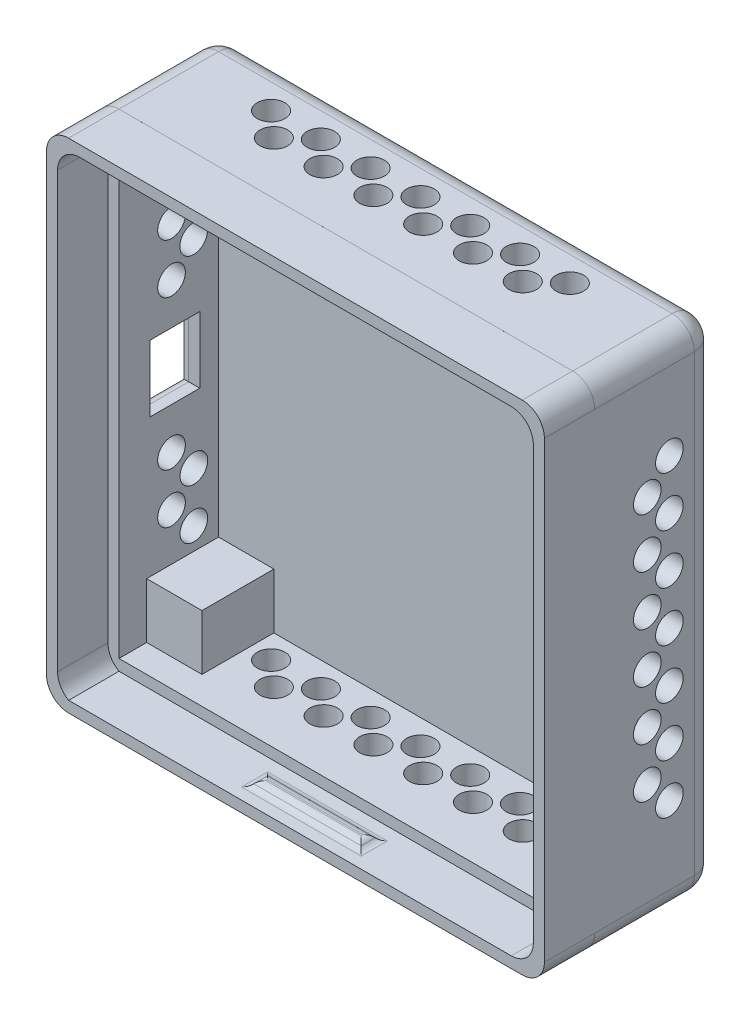
SolidWorks part; units mm, degrees
ref_plane "Piano frontale" through (0, 0, 0) normal (0, 0, 1) x (1, 0, 0)
ref_plane "Piano superiore" through (0, 0, 0) normal (0, 1, 0) x (1, 0, 0)
ref_plane "Piano destro" through (0, 0, 0) normal (1, 0, 0) x (0, 0, -1)
sketch "Schizzo2" plane through (0, 0, 0) normal (0, 0, 1) x (1, 0, 0)
  line L1 (0, 0) -> (45, 0)
  line L2 (0, 0) -> (0, 45)
  line L3 (0, 45) -> (45, 45)
  line L4 (45, 0) -> (45, 45)
  dimension "D1" = 45
  dimension "D2" = 45
extrude "Estrusione-Estrusione2" add sketch "Schizzo2" along normal blind 11
shell "Svuota1" thickness 2 removed face at (22.5, 22.5, 11)
fillet "Raccordo1" radius 2 4 edges at (45, 45, 5.5) (45, 0, 5.5) (0, 0, 5.5) (0, 45, 5.5)
fillet "Raccordo2" radius 2 8 edges at (44.4142, 0.5858, 0) (22.5, 0, 0) (0.5858, 0.5858, 0) (0, 22.5, 0) (0.5858, 44.4142, 0) (22.5, 45, 0) (44.4142, 44.4142, 0) (45, 22.5, 0)
sketch "Schizzo3" plane through (0, 0, 2) normal (0, 0, 1) x (1, 0, 0)
  line L0 (43, 43) -> (2, 43) construction
  line L1 (2, 43) -> (7, 43)
  line L2 (2, 43) -> (2, 38)
  line L3 (2, 38) -> (7, 38)
  line L4 (7, 43) -> (7, 38)
  line L5 (43, 43) -> (2, 43) construction
  dimension "D1" = 5
  dimension "D2" = 5
extrude "Estrusione-Estrusione3" add sketch "Schizzo3" along normal blind 6.5
sketch "Schizzo4" plane through (0, 0, 2) normal (0, 0, 1) x (1, 0, 0)
  line L1 (43, 2) -> (38, 2)
  line L2 (43, 2) -> (43, 7)
  line L3 (43, 7) -> (38, 7)
  line L4 (38, 2) -> (38, 7)
  dimension "D1" = 5
  dimension "D2" = 5
extrude "Estrusione-Estrusione4" add sketch "Schizzo4" along normal blind 6.5
fillet "Raccordo3" radius 4 2 edges at (38, 7, 5.25) (7, 38, 5.25)
sketch "Schizzo5" plane through (0, 0, 2) normal (0, 0, 1) x (1, 0, 0)
  line L0 (43, 2) -> (43, 43) construction
  line L1 (43, 43) -> (38, 43)
  line L2 (43, 43) -> (43, 38)
  line L3 (43, 38) -> (38, 38)
  line L4 (38, 43) -> (38, 38)
  line L5 (43, 43) -> (7, 43) construction
  line L7 (2, 2) -> (7, 2)
  line L8 (2, 2) -> (2, 7)
  line L9 (2, 7) -> (7, 7)
  line L10 (7, 2) -> (7, 7)
  dimension "D1" = 5
  dimension "D2" = 5
  dimension "D3" = 5
  dimension "D4" = 5
extrude "Estrusione-Estrusione5" add sketch "Schizzo5" along normal blind 6.5 contours L2 L1 L4 L3 | L8 L7 L10 L9
sketch "Schizzo12" plane through (0, 0, 11) normal (0, 0, 1) x (1, 0, 0)
  line L1 (0, 44.9999) -> (45, 44.9999)
  line L2 (0, 44.9999) -> (0, 43.9999)
  line L3 (0, 43.9999) -> (45, 43.9999)
  line L4 (45, 44.9999) -> (45, 43.9999)
  dimension "D1" = 45
  dimension "D2" = 1
extrude "Estrusione-Estrusione7" add sketch "Schizzo12" along normal blind 4.55
sketch "Schizzo13" plane through (0, 0, 11) normal (0, 0, 1) x (1, 0, 0)
  line L1 (45, 43.9999) -> (44, 43.9999)
  line L2 (45, 43.9999) -> (45, -0.0001)
  line L3 (45, -0.0001) -> (44, -0.0001)
  line L4 (44, 43.9999) -> (44, -0.0001)
  dimension "D1" = 44
  dimension "D2" = 1
extrude "Estrusione-Estrusione10" add sketch "Schizzo13" along normal blind 4.55
sketch "Schizzo15" plane through (0, 0, 11) normal (0, 0, 1) x (1, 0, 0)
  line L1 (44, -0.0001) -> (2, -0.0001)
  line L2 (44, -0.0001) -> (44, 0.9999)
  line L3 (44, 0.9999) -> (2, 0.9999)
  line L4 (2, -0.0001) -> (2, 0.9999)
  dimension "D1" = 1
  dimension "D2" = 42
extrude "Estrusione-Estrusione11" add sketch "Schizzo15" along normal blind 4.55
fillet "Raccordo4" radius 2 1 edges at (45, -0.0001, 13.275)
fillet "Raccordo5" radius 2 1 edges at (45, 44.9999, 13.275)
sketch "Schizzo17" plane through (0, 0, 11) normal (0, 0, 1) x (1, 0, 0)
  line L1 (0, 43.9999) -> (1, 43.9999)
  line L2 (0, 43.9999) -> (0, -0.0001)
  line L3 (0, -0.0001) -> (1, -0.0001)
  line L4 (1, 43.9999) -> (1, -0.0001)
  dimension "D1" = 1
  dimension "D2" = 44
extrude "Estrusione-Estrusione13" add sketch "Schizzo17" along normal blind 4.55
fillet "Raccordo6" radius 2 1 edges at (0, 44.9999, 13.275)
fillet "Raccordo7" radius 2 1 edges at (44, 0.9999, 13.275)
fillet "Raccordo8" radius 2 1 edges at (44, 43.9999, 13.275)
fillet "Raccordo9" radius 2 1 edges at (1, 43.9999, 13.275)
sketch "Schizzo18" plane through (0, 0, 11) normal (0, 0, 1) x (1, 0, 0)
  line L0 (1, -0.0001) -> (1, 41.9999) construction
  line L1 (2, -0.0001) -> (1, -0.0001)
  line L2 (2, -0.0001) -> (2, 0.9995)
  line L3 (2, 0.9995) -> (1, 0.9995)
  line L4 (1, -0.0001) -> (1, 0.9995)
extrude "Estrusione-Estrusione14" add sketch "Schizzo18" along normal blind 4.55
fillet "Raccordo10" radius 2 1 edges at (0, -0.0001, 13.275)
fillet "Raccordo11" radius 2 1 edges at (1, 0.9995, 13.275)
sketch "Schizzo22" plane through (0, 0.9999, 0) normal (0, 1, 0) x (1, 0, 0)
  line L5 (17.0049, -12.5647) -> (27.0049, -12.5647)
  line L6 (17.0049, -12.5647) -> (17.0049, -14.1147)
  line L7 (17.0049, -14.1147) -> (27.0049, -14.1147)
  line L8 (27.0049, -12.5647) -> (27.0049, -14.1147)
  dimension "D1" = 1.55
  dimension "D2" = 10
extrude "Estrusione-Estrusione15" add sketch "Schizzo22" along normal blind 0.5
fillet "Raccordo17" radius 0.74 4 edges at (27.0049, 1.4999, 13.3397) (22.0049, 1.4999, 14.1147) (17.0049, 1.4999, 13.3397) (22.0049, 1.4999, 12.5647)
fillet "Raccordo18" radius 0.74 4 edges at (22.0049, 0.9999, 12.5647) (27.0049, 0.9999, 13.3397) (17.0049, 0.9999, 13.3397) (22.0049, 0.9999, 14.1147)
sketch "Schizzo30" plane through (0, 43.9999, 0) normal (0, -1, 0) x (1, 0, 0)
  line L1 (17.0049, 14.1147) -> (27.0049, 14.1147)
  line L2 (17.0049, 14.1147) -> (17.0049, 12.5647)
  line L3 (17.0049, 12.5647) -> (27.0049, 12.5647)
  line L4 (27.0049, 14.1147) -> (27.0049, 12.5647)
extrude "Estrusione-Estrusione20" add sketch "Schizzo30" along normal blind 0.5 draft 1
fillet "Raccordo19" radius 0.74 4 edges at (22.0049, 43.4999, 12.5735) (26.9962, 43.4999, 13.3397) (22.0049, 43.4999, 14.106) (17.0136, 43.4999, 13.3397)
fillet "Raccordo20" radius 0.74 4 edges at (17.0049, 43.9999, 13.3397) (22.0049, 43.9999, 12.5647) (27.0049, 43.9999, 13.3397) (22.0049, 43.9999, 14.1147)
sketch "Schizzo34" plane through (43, 0, 0) normal (-1, 0, 0) x (0, 0, 1)
  circle A0 centre (4.2516, 35.9994) radius 1.25
  circle A1 centre (4.2516, 31.5034) radius 1.25
  circle A2 centre (4.2516, 27.0032) radius 1.25
  circle A3 centre (4.2516, 22.5053) radius 1.25
  circle A4 centre (4.2516, 18.0015) radius 1.25
  circle A5 centre (4.2516, 13.5036) radius 1.25
  circle A6 centre (4.2516, 9.0038) radius 1.25
  dimension "D1" = 2.5
  dimension "D2" = 2.5
  dimension "D3" = 2.5
  dimension "D4" = 2.5
  dimension "D5" = 2.5
  dimension "D6" = 2.5
  dimension "D7" = 2.5
extrude "Taglio-Estrusione7" cut sketch "Schizzo34" against normal blind 2
sketch "Schizzo35" plane through (43, 0, 0) normal (-1, 0, 0) x (0, 0, 1)
  circle A0 centre (6.2524, 33.7503) radius 1.25
  circle A1 centre (6.2524, 29.2487) radius 1.25
  circle A2 centre (6.2524, 24.7505) radius 1.25
  circle A3 centre (6.2524, 20.2517) radius 1.25
  circle A4 centre (6.2524, 15.7547) radius 1.25
  circle A5 centre (6.2524, 11.252) radius 1.25
  dimension "D1" = 2.5
  dimension "D2" = 2.5
  dimension "D3" = 2.5
  dimension "D4" = 2.5
  dimension "D5" = 2.5
  dimension "D6" = 2.5
extrude "Taglio-Estrusione8" cut sketch "Schizzo35" against normal blind 2
sketch "Schizzo36" plane through (0, 2, 0) normal (0, 1, 0) x (1, 0, 0)
  circle A0 centre (35.9868, -4.2536) radius 1.25
  circle A1 centre (31.4911, -4.2536) radius 1.25
  circle A2 centre (26.996, -4.2536) radius 1.25
  circle A3 centre (22.4971, -4.2536) radius 1.25
  circle A4 centre (17.9983, -4.2536) radius 1.25
  circle A5 centre (13.4999, -4.2536) radius 1.25
  circle A6 centre (9.0039, -4.2536) radius 1.25
  dimension "D1" = 2.5
  dimension "D2" = 2.5
  dimension "D3" = 2.5
  dimension "D4" = 2.5
  dimension "D5" = 2.5
  dimension "D6" = 2.5
  dimension "D7" = 2.5
extrude "Taglio-Estrusione9" cut sketch "Schizzo36" against normal blind 2
sketch "Schizzo37" plane through (0, 2, 0) normal (0, 1, 0) x (1, 0, 0)
  circle A0 centre (33.7463, -6.2534) radius 1.25
  circle A1 centre (29.2472, -6.2534) radius 1.25
  circle A2 centre (24.7485, -6.2534) radius 1.25
  circle A3 centre (20.2458, -6.2534) radius 1.25
  circle A4 centre (15.749, -6.2534) radius 1.25
  circle A5 centre (11.2492, -6.2534) radius 1.25
  dimension "D1" = 2.5
  dimension "D2" = 2.5
  dimension "D3" = 2.5
  dimension "D4" = 2.5
  dimension "D5" = 2.5
  dimension "D6" = 2.5
extrude "Taglio-Estrusione10" cut sketch "Schizzo37" against normal blind 2
sketch "Schizzo38" plane through (0, 43, 0) normal (0, -1, 0) x (-1, 0, 0)
  circle A0 centre (-8.9935, -4.2481) radius 1.25
  circle A1 centre (-13.4899, -4.2481) radius 1.25
  circle A2 centre (-17.9905, -4.2481) radius 1.25
  circle A3 centre (-22.4934, -4.2481) radius 1.25
  circle A4 centre (-26.9933, -4.2481) radius 1.25
  circle A5 centre (-31.495, -4.2481) radius 1.25
  circle A6 centre (-35.9965, -4.2481) radius 1.25
  dimension "D1" = 2.5
  dimension "D2" = 2.5
  dimension "D3" = 2.5
  dimension "D4" = 2.5
  dimension "D5" = 2.5
  dimension "D6" = 2.5
  dimension "D7" = 2.5
extrude "Taglio-Estrusione11" cut sketch "Schizzo38" against normal blind 2
sketch "Schizzo39" plane through (0, 43, 0) normal (0, -1, 0) x (-1, 0, 0)
  circle A0 centre (-11.2508, -6.2534) radius 1.25
  circle A1 centre (-15.7484, -6.2534) radius 1.25
  circle A2 centre (-20.2458, -6.2534) radius 1.25
  circle A3 centre (-24.7485, -6.2534) radius 1.25
  circle A4 centre (-29.2472, -6.2534) radius 1.25
  circle A5 centre (-33.7463, -6.2534) radius 1.25
  dimension "D1" = 2.5
  dimension "D2" = 2.5
  dimension "D3" = 2.5
  dimension "D4" = 2.5
  dimension "D5" = 2.5
  dimension "D6" = 2.5
extrude "Taglio-Estrusione12" cut sketch "Schizzo39" against normal blind 2
sketch "Schizzo40" plane through (2, 0, 0) normal (1, 0, 0) x (0, 0, -1)
  circle A0 centre (-4.2347, 8.9988) radius 1.25
  circle A1 centre (-4.2347, 13.4961) radius 1.25
  circle A2 centre (-4.2527, 35.9982) radius 1.25
  circle A3 centre (-4.2527, 31.4945) radius 1.25
  dimension "D1" = 2.5
  dimension "D2" = 2.5
  dimension "D5" = 2.5
  dimension "D6" = 2.5
sketch "Schizzo42" plane through (2, 0, 0) normal (1, 0, 0) x (0, 0, -1)
  line L0 (-8.2, 25.5052) -> (-3.7, 25.5052)
  line L5 (-8.2, 25.5052) -> (-8.2, 19.5052)
  line L6 (-8.2, 19.5052) -> (-3.7, 19.5052)
  line L7 (-3.7, 25.5052) -> (-3.7, 19.5052)
  dimension "D1" = 6
  dimension "D2" = 4.5
extrude "Taglio-Estrusione13" cut sketch "Schizzo42" against normal blind 2
fillet "Raccordo21" radius 1 4 edges at (0, 19.5052, 5.95) (0, 22.5052, 3.7) (0, 25.5052, 5.95) (0, 22.5052, 8.2)
extrude "Taglio-Estrusione14" cut sketch "Schizzo40" against normal blind 2
sketch "Schizzo43" plane through (2, 0, 0) normal (1, 0, 0) x (0, 0, -1)
  circle A0 centre (-6.2524, 11.2507) radius 1.25
  circle A1 centre (-6.2524, 15.7515) radius 1.25
  circle A2 centre (-6.2524, 29.2485) radius 1.25
  circle A3 centre (-6.2524, 33.7503) radius 1.25
  dimension "D1" = 2.5
  dimension "D2" = 2.5
  dimension "D3" = 2.5
  dimension "D4" = 2.5
extrude "Taglio-Estrusione15" cut sketch "Schizzo43" against normal blind 2
sketch "Schizzo44" plane through (0, 0, 0) normal (-1, 0, 0) x (0, 0, 1)
  line L1 (10.7483, 26.35) -> (13.3283, 26.35)
  line L2 (10.7483, 26.35) -> (10.7483, 25.75)
  line L3 (10.7483, 25.75) -> (13.3283, 25.75)
  line L4 (13.3283, 26.35) -> (13.3283, 25.75)
  point P4 (0, 0)
  dimension "D1" = 0.6
  dimension "D2" = 2.58
extrude "Estrusione-Estrusione21" add sketch "Schizzo44" along normal blind 0.7
sketch "Schizzo45" plane through (0, 0, 0) normal (-1, 0, 0) x (0, 0, 1)
  circle A0 centre (12.036, 19.7623) radius 1.29
  circle A1 centre (12.036, 19.7623) radius 1
  dimension "D1" = 2.58
  dimension "D2" = 2
extrude "Estrusione-Estrusione22" add sketch "Schizzo45" along normal blind 0.7
fillet "Raccordo23" radius 0.1 6 edges at (-0.7, 26.05, 13.3283) (-0.7, 25.75, 12.0383) (-0.7, 26.05, 10.7483) (-0.7, 26.35, 12.0383) (-0.7, 19.7623, 13.326) (-0.7, 19.7623, 13.036)
